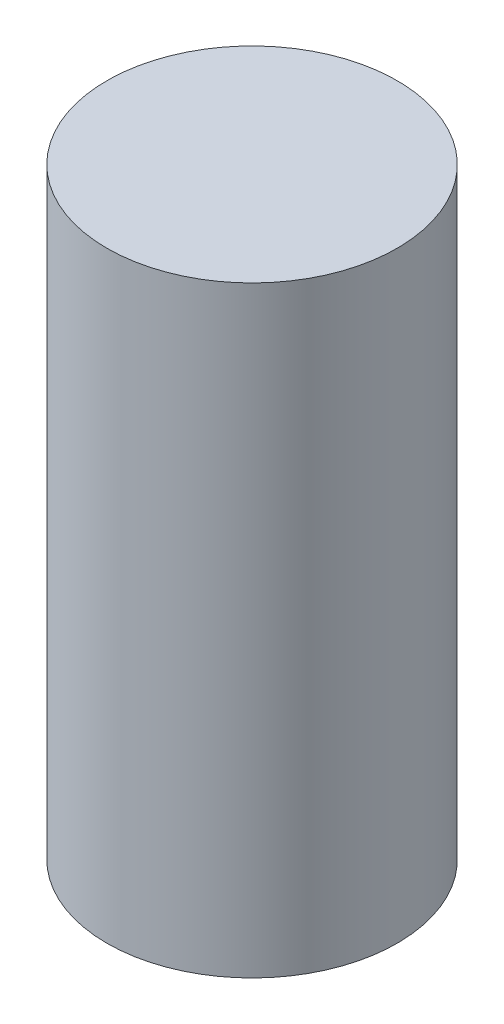
SolidWorks part; units mm, degrees
ref_plane "Front Plane" through (0, 0, 0) normal (0, 0, 1) x (1, 0, 0)
ref_plane "Top Plane" through (0, 0, 0) normal (0, 1, 0) x (1, 0, 0)
ref_plane "Right Plane" through (0, 0, 0) normal (1, 0, 0) x (0, 0, -1)
sketch "Sketch1" plane through (0, 0, 0) normal (0, 1, 0) x (1, 0, 0)
  circle A0 centre (0, 0) radius 3
  dimension "D1" = 6
extrude "Boss-Extrude1" add sketch "Sketch1" along normal blind 12.44
equation "\"bearing_21_OD\"= 21mm"
equation "\"pin_cirlce_diameter\"= 75mm"
equation "\"pin_diam\"= 6mm"
equation "\"gear_thickness\"= 4mm"
equation "\"ball_bearing_diam\"= 2.96mm"
equation "\"bearing_21_outer_clearance\"= 0.127mm'change this"
equation "\"bearing_15_OD\"= 15mm"
equation "\"bearing_15_outer_clearance\"= 0mm'change this"
equation "\"thrust_bearing_thickness\"= 5mm'measure this irl and change"
equation "\"D1@Boss-Extrude1\"=\"ball_bearing_diam\"*1.50+2*\"gear_thickness\""
